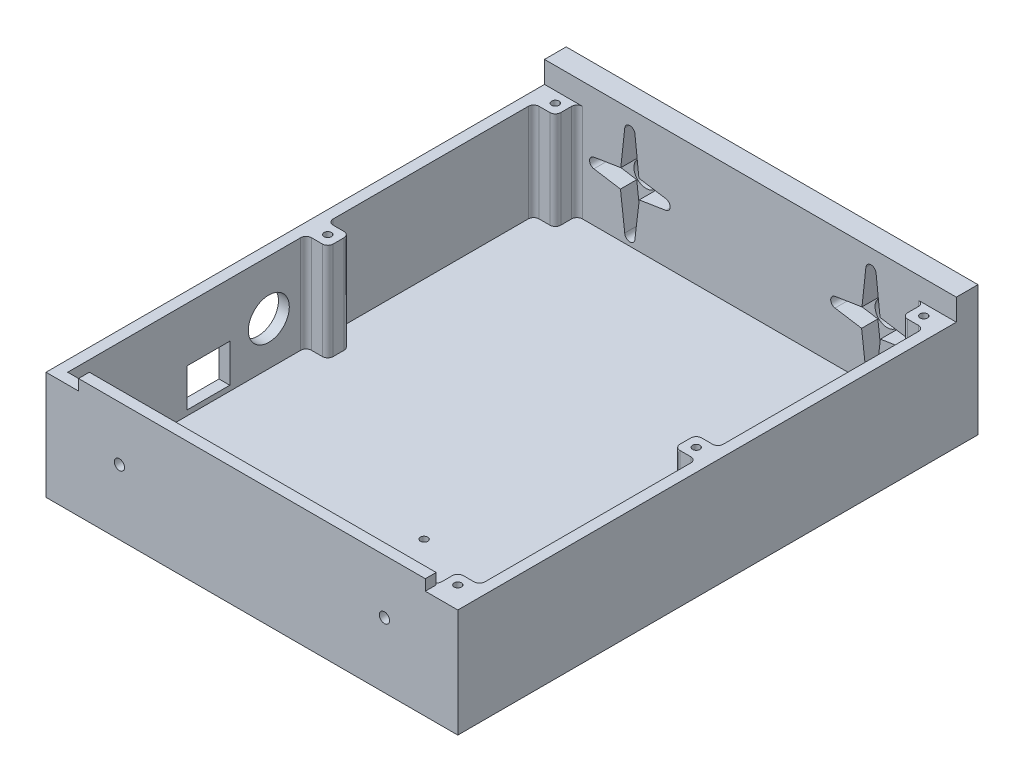
SolidWorks part; units mm, degrees
material "ABS"
ref_plane "Front" through (0, 0, 0) normal (0, 0, 1) x (1, 0, 0)
ref_plane "Top" through (0, 0, 0) normal (0, 1, 0) x (1, 0, 0)
ref_plane "Right" through (0, 0, 0) normal (1, 0, 0) x (0, 0, -1)
sketch "Sketch1" plane through (0, 0, 0) normal (0, 1, 0) x (1, 0, 0)
  line L1 (-60.325, 76.2) -> (60.325, 76.2)
  line L2 (-60.325, 76.2) -> (-60.325, -76.2)
  line L3 (-60.325, -76.2) -> (60.325, -76.2)
  line L4 (60.325, 76.2) -> (60.325, -76.2)
  line L5 (-60.325, 76.2) -> (60.325, -76.2) construction
  line L6 (-60.325, -76.2) -> (60.325, 76.2) construction
  line L11 (-57.15, 69.85) -> (57.15, 69.85)
  line L12 (-57.15, 69.85) -> (-57.15, -73.025)
  line L13 (-57.15, -73.025) -> (57.15, -73.025)
  line L14 (57.15, 69.85) -> (57.15, -73.025)
  point P0 (0, 0)
  point P6 (0, 0)
  dimension "D1" = 3.175
  dimension "D2" = 152.4
  dimension "D3" = 114.3
  dimension "D4" = 3.175
  dimension "D5" = 3.175
  dimension "D6" = 6.35
extrude "Boss-Extrude1" add sketch "Sketch1" along normal blind 3.175 contours L4 L3 L2 L1
extrude "Boss-Extrude2" add sketch "Sketch1<3>" along normal blind 38.1
sketch "Sketch1<3>" plane through (0, 0, 0) normal (0, 1, 0) x (1, 0, 0) same geometry as "Sketch1"
sketch "Sketch2" plane through (0, 0, 76.2) normal (0, 0, 1) x (1, 0, 0)
  line L0 (38.825, 19.05) -> (60.325, 19.05) construction
  line L1 (60.325, 38.1) -> (60.325, 0) construction
  circle A0 centre (38.825, 19.05) radius 1.5
  dimension "D2" = 3
  dimension "D1" = 21.5
extrude "Cut-Extrude1" cut sketch "Sketch2" against normal up to surface (3.175 mm away) up to face at (0, 20.6375, 73.025)
sketch "Sketch3" plane through (0, 0, -69.85) normal (0, 0, 1) x (1, 0, 0)
  line L0 (60.325, 19.05) -> (35.325, 19.05) construction
  line L1 (60.325, 38.1) -> (60.325, 0) construction
  line L2 (36.825, 5.8) -> (38.138, 16.8438)
  line L3 (33.825, 5.8) -> (32.5119, 16.8438)
  line L4 (32.6352, 21.4049) -> (33.8337, 32.4617)
  line L5 (38.0148, 21.4049) -> (36.8163, 32.4617)
  line L6 (24.7882, 17.5688) -> (33.1188, 16.2369)
  line L7 (24.7882, 20.5312) -> (33.1188, 21.863)
  line L9 (33.1188, 21.863) -> (33.1188, 16.2369) construction
  line L10 (37.5312, 21.863) -> (45.8618, 20.5312)
  line L11 (37.5312, 16.237) -> (45.8618, 17.5688)
  arc A0 (32.6352, 21.4049) -> (32.5119, 16.8438) centre (35.325, 19.05) ccw
  arc A1 (33.825, 5.8) -> (36.825, 5.8) centre (35.325, 5.8) ccw
  arc A2 (32.6352, 21.4049) -> (32.5119, 16.8438) centre (35.325, 19.05) ccw construction
  arc A10 (33.8337, 32.4617) -> (36.8163, 32.4617) centre (35.325, 32.3) cw
  arc A11 (38.138, 16.8438) -> (38.0148, 21.4049) centre (35.325, 19.05) ccw
  arc A12 (38.138, 16.8438) -> (38.0148, 21.4049) centre (35.325, 19.05) ccw construction
  arc A13 (24.7882, 20.5312) -> (24.7882, 17.5688) centre (25.025, 19.05) ccw
  arc A14 (37.5312, 21.863) -> (37.5312, 16.237) centre (35.325, 19.05) cw
  arc A15 (33.1188, 16.2369) -> (33.1188, 21.863) centre (35.325, 19.05) cw
  arc A16 (45.8618, 20.5312) -> (45.8618, 17.5688) centre (45.625, 19.05) cw
  circle A17 centre (35.325, 19.05) radius 3.575
  dimension "D1" = 7.15
  dimension "D3" = 3
  dimension "D6" = 14.75
  dimension "D7" = 3
  dimension "D2" = 25
  dimension "D4" = 14.75
  dimension "D5" = 5.6261
  dimension "D8" = 5.6261
  dimension "D9" = 11.8
extrude "Cut-Extrude8" cut sketch "Sketch3" against normal blind 4.7625 contours A16 L10 L5 A11 L2 L11 | A17 L10 L5 A10 L4 L7 | A17 L6 L3 A1 L2 L11 | L4 A15 L7 | L2 A14 L11 | L6 A15 L3 | L6 A15 L7 A13 | A14 L11 A16 L10 region at (35.325, 10.8168, -69.85) region at (37.9239, 16.4606, -69.85) region at (42.2416, 19.0536, -69.85) region at (32.7261, 16.4606, -69.85) region at (35.325, 27.3342, -69.85) region at (32.8048, 21.6911, -69.85)
extrude "Cut-Extrude9" cut sketch "Sketch3<8>" against normal through all contours A14 A17 A15 A0 A11 region at (35.325, 19.05, -69.85)
sketch "Sketch3<8>" plane through (0, 0, -69.85) normal (0, 0, 1) x (1, 0, 0) same geometry as "Sketch3"
mirror "Mirror1" about plane through (0, 0, 0) normal (1, 0, 0) of "Cut-Extrude9", "Cut-Extrude1", "Cut-Extrude8"
sketch "Sketch4" plane through (-57.15, 0, 0) normal (1, 0, 0) x (0, 0, -1)
  line L0 (-73.025, 15.876) -> (-38.025, 15.876) construction
  line L1 (-73.025, 38.1) -> (-73.025, 3.175) construction
  line L2 (-25.525, 15.876) -> (-14.095, 15.876) construction
  line L3 (-38.025, 15.876) -> (-25.525, 15.876)
  line L4 (-38.025, 15.876) -> (-38.025, 4.7)
  line L5 (-38.025, 4.7) -> (-25.525, 4.7)
  line L6 (-25.525, 15.876) -> (-25.525, 4.7)
  line L7 (76.2, 0) -> (-76.2, 0) construction
  circle A0 centre (-14.095, 15.876) radius 6
  point P11 (0, 0)
  point P13 (0, 0)
  point P14 (-25.525, 12.9034)
  point P15 (0, 0)
  point P16 (0, 0)
  point P17 (-25.525, 16.2755)
  dimension "D5" = 12
  dimension "D1" = 35
  dimension "D2" = 11.176
  dimension "D3" = 12.5
  dimension "D4" = 4.7
  dimension "D6" = 11.43
extrude "Cut-Extrude10" cut sketch "Sketch4" against normal up to next
sketch "Sketch5" plane through (0, 3.175, 0) normal (0, 1, 0) x (1, 0, 0)
  line L0 (-57.15, -34.596) -> (8.85, -34.596) construction
  line L1 (-57.15, 69.85) -> (-57.15, -73.025) construction
  line L2 (-60.325, -38.025) -> (-57.15, -38.025) construction
  line L3 (8.85, -34.596) -> (8.85, -62.6122) construction
  point P7 (8.85, -34.596)
  point P9 (8.85, -62.6122)
  dimension "D1" = 3.429
  dimension "D2" = 66
  dimension "D3" = 28.0162
hole_wizard "#2 Clearance Hole1" positions "3DSketch1" profile "Sketch7" hole size "#2" standard "ANSI Inch" end condition up to next
sketch3d "3DSketch1"
  point P0 (8.85, 3.175, 62.6122)
  point P3 (8.85, 3.175, 34.596)
sketch "Sketch7" plane through (8.85, 3.175, 62.6122) normal (1, 0, 0) x (0, 0, 1)
  line L0 (0, 0) -> (0, 3.175)
  line L1 (0, 3.175) -> (1.0795, 3.175)
  line L2 (1.0795, 3.175) -> (1.0795, 0)
  line L5 (1.0795, 0) -> (0, 0)
  line L11 (0, -6.35) -> (0, 107.95) construction
  dimension "Thru Hole Dia." = 2.159
  dimension "Thru Hole Depth" = 3.175
sketch "Sketch8" plane through (0, 38.1, 0) normal (0, 1, 0) x (1, 0, 0)
  line L1 (-60.325, -76.2) -> (-50.8, -76.2)
  line L2 (-60.325, -76.2) -> (-60.325, 69.85)
  line L3 (-60.325, 69.85) -> (-50.8, 69.85)
  line L4 (-50.8, -76.2) -> (-50.8, 69.85)
  line L5 (60.325, -76.2) -> (50.8, -76.2)
  line L6 (60.325, -76.2) -> (60.325, 69.85)
  line L7 (60.325, 69.85) -> (50.8, 69.85)
  line L8 (50.8, -76.2) -> (50.8, 69.85)
  line L9 (-60.325, 69.85) -> (60.325, 69.85)
  line L10 (-60.325, 69.85) -> (-60.325, -76.2)
  line L11 (-60.325, -76.2) -> (60.325, -76.2)
  line L12 (60.325, 69.85) -> (60.325, -76.2)
  line M8 (60.325, -76.2) -> (60.325, 76.2)
  line M10 (-60.325, 76.2) -> (-60.325, -76.2)
  line M11 (-60.325, -76.2) -> (60.325, -76.2)
  line M12 (57.15, -73.025) -> (-57.15, -73.025)
  line M13 (-57.15, -73.025) -> (-57.15, 69.85)
  line M15 (57.15, 69.85) -> (57.15, -73.025)
  dimension "D1" = 9.525
  dimension "D2" = 146.05
extrude "Cut-Extrude11" cut sketch "Sketch8" against normal blind 3.175 contours L9 L4 L8 M12 | L4 L3 M12 M13 | L4 L3 M11 M12 M13 M10 | L8 L7 M12 M15 | L8 L7 M11 M8 M15 M12 | L10 L9 L12 L11 region at (-58.5391, 38.1, 6.1516) region at (-53.975, 38.1, 1.5875) region at (0, 38.1, 1.5875) region at (58.5391, 38.1, 6.1516) region at (53.975, 38.1, 1.5875)
extrude "Cut-Extrude13" cut sketch "Sketch8<6>" against normal blind 6.35 contours L4 L3 M11 M12 M13 M10 | L4 L3 M12 M13 | L8 L7 M12 M15 | L8 L7 M11 M8 M15 M12 region at (-58.5391, 38.1, 6.1516) region at (-53.975, 38.1, 1.5875) region at (58.5391, 38.1, 6.1516) region at (53.975, 38.1, 1.5875)
sketch "Sketch8<6>" plane through (0, 38.1, 0) normal (0, 1, 0) x (1, 0, 0) same geometry as "Sketch8"
sketch "Sketch9" plane through (0, 3.175, 0) normal (0, 1, 0) x (1, 0, 0)
  line L0 (-57.15, 69.85) -> (-57.15, -73.025) construction
  line L1 (-50.8, -3.175) -> (-57.15, -3.175)
  line L2 (-50.8, -3.175) -> (-50.8, 3.175)
  line L3 (-50.8, 3.175) -> (-57.15, 3.175)
  line L4 (-57.15, -3.175) -> (-57.15, 3.175)
  line L5 (-50.8, -3.175) -> (-57.15, 3.175) construction
  line L6 (-50.8, 3.175) -> (-57.15, -3.175) construction
  line L7 (57.15, -73.025) -> (57.15, 69.85) construction
  line L8 (50.8, 3.175) -> (57.15, 3.175)
  line L9 (50.8, 3.175) -> (50.8, -3.175)
  line L10 (50.8, -3.175) -> (57.15, -3.175)
  line L11 (57.15, 3.175) -> (57.15, -3.175)
  line L12 (50.8, 3.175) -> (57.15, -3.175) construction
  line L13 (50.8, -3.175) -> (57.15, 3.175) construction
  line L15 (57.15, -73.025) -> (50.8, -73.025)
  line L16 (57.15, -73.025) -> (57.15, -66.675)
  line L17 (57.15, -66.675) -> (50.8, -66.675)
  line L18 (50.8, -73.025) -> (50.8, -66.675)
  line L19 (-57.15, 69.85) -> (-50.8, 69.85)
  line L20 (-57.15, 69.85) -> (-57.15, 63.5)
  line L21 (-57.15, 63.5) -> (-50.8, 63.5)
  line L22 (-50.8, 69.85) -> (-50.8, 63.5)
  line L23 (57.15, 69.85) -> (50.8, 69.85)
  line L24 (57.15, 69.85) -> (57.15, 63.5)
  line L25 (57.15, 63.5) -> (50.8, 63.5)
  line L26 (50.8, 69.85) -> (50.8, 63.5)
  point P0 (-53.975, 0)
  point P9 (53.975, 0)
  dimension "D1" = 6.35
extrude "Boss-Extrude3" add sketch "Sketch9" along normal up to surface (28.575 mm away) up to face at (-56.0917, 31.75, 26.4583)
fillet "Fillet1" radius 1.5875 17 edges at (57.15, 17.4625, 66.675) (50.8, 17.4625, 66.675) (50.8, 17.4625, 73.025) (57.15, 17.4625, -3.175) (50.8, 17.4625, -3.175) (50.8, 17.4625, 3.175) (57.15, 17.4625, 3.175) (-57.15, 17.4625, -3.175) (-50.8, 17.4625, -3.175) (-50.8, 17.4625, 3.175) (-57.15, 17.4625, 3.175) (57.15, 17.4625, -63.5) (50.8, 17.4625, -63.5) (50.8, 17.4625, -69.85) (-57.15, 17.4625, -63.5) (-50.8, 17.4625, -63.5) (-50.8, 17.4625, -69.85)
hole_wizard "#2 Clearance Hole2" positions "Sketch10" profile "Sketch12" hole size "#2" standard "ANSI Inch"
sketch "Sketch10" plane through (0, 31.75, 0) normal (0, 1, 0) x (1, 0, 0)
  line L0 (-53.975, 3.175) -> (-53.975, -3.175) construction
  line L1 (-52.3875, 3.175) -> (-55.5625, 3.175) construction
  line L2 (-55.5625, -3.175) -> (-52.3875, -3.175) construction
  line L4 (53.975, 3.175) -> (53.975, -3.175) construction
  line L5 (55.5625, 3.175) -> (52.3875, 3.175) construction
  line L6 (52.3875, -3.175) -> (55.5625, -3.175) construction
  line L8 (53.975, -66.675) -> (53.975, -69.85) construction
  line L9 (55.5625, -66.675) -> (52.3875, -66.675) construction
  line L10 (53.975, -69.85) -> (50.8, -69.85) construction
  line L11 (50.8, -68.2625) -> (50.8, -71.4375) construction
  line L12 (-53.975, 63.5) -> (-53.975, 66.675) construction
  line L13 (-55.5625, 63.5) -> (-52.3875, 63.5) construction
  line L14 (-53.975, 66.675) -> (-50.8, 66.675) construction
  line L15 (-50.8, 65.0875) -> (-50.8, 68.2625) construction
  line L17 (50.8, 66.675) -> (53.975, 66.675) construction
  line L18 (50.8, 68.2625) -> (50.8, 65.0875) construction
  line L19 (53.975, 66.675) -> (53.975, 63.5) construction
  line L20 (52.3875, 63.5) -> (55.5625, 63.5) construction
  point P19 (53.975, -69.85)
  point P30 (53.975, 0)
  point P32 (-53.975, 0)
  point P35 (-53.975, 66.675)
  point P44 (53.975, 66.675)
sketch "Sketch12" plane through (53.975, 31.75, -66.675) normal (1, 0, 0) x (0, 0, 1)
  line L0 (0, 0) -> (0, 13.3486)
  line L1 (0, 13.3486) -> (1.0795, 12.7)
  line L2 (1.0795, 12.7) -> (1.0795, 0)
  line L5 (1.0795, 0) -> (0, 0)
  line L10 (0, 13.3486) -> (-1.0795, 12.7) construction
  line L11 (0, -6.35) -> (0, 107.95) construction
  dimension "Hole Dia." = 2.159
  dimension "Hole Depth" = 12.7
  dimension "Drill Angle" = 118
